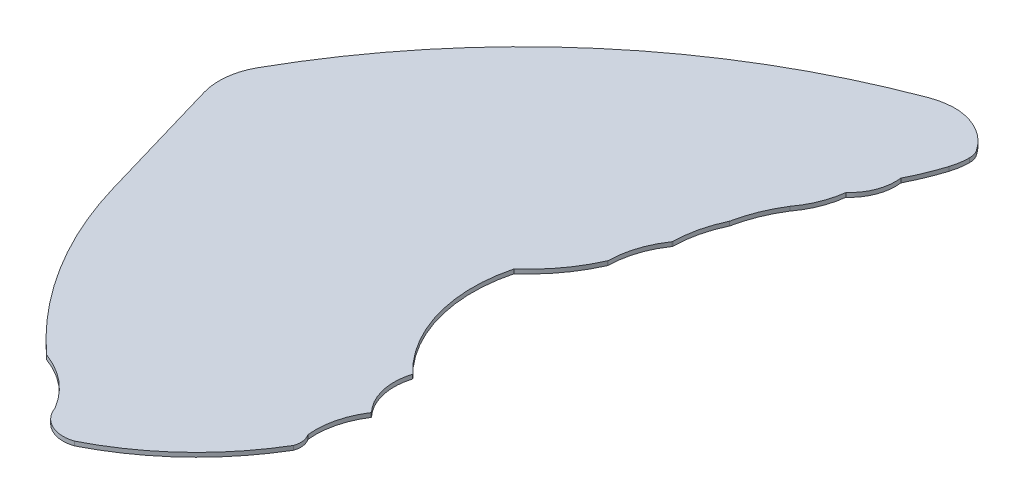
SolidWorks part; units mm, degrees
ref_plane "Plano frontal" through (0, 0, 0) normal (0, 0, 1) x (1, 0, 0)
ref_plane "Plano superior" through (0, 0, 0) normal (0, 1, 0) x (1, 0, 0)
ref_plane "Plano direito" through (0, 0, 0) normal (1, 0, 0) x (0, 0, -1)
sketch "Esboço1" plane through (0, 0, 0) normal (0, 1, 0) x (1, 0, 0)
  line L0 (245.8971, 320.852) -> (1229.6128, 320.852) construction
  line L1 (16.8906, -92.872) -> (-2.8919, -25.3314)
  line L3 (11.8593, -37.4647) -> (16.8906, -86.1328)
  arc A0 (-2.8919, -25.3314) -> (0, 0) centre (28.6286, -16.0991) cw
  arc A1 (0, 0) -> (189.3972, 162.1056) centre (316.3195, -177.8795) cw
  arc A3 (225.6385, 150.4697) -> (227.1081, 145.6019) centre (218.3116, 145.6019) cw construction
  arc A4 (227.1081, 145.6019) -> (225.6385, 136.1666) centre (196.0862, 145.6019) cw construction
  arc A5 (225.6385, 136.1666) -> (218.3116, 118.3563) centre (112.5985, 172.257) cw construction
  arc A7 (218.3116, 118.3563) -> (210.4763, 97.5461) centre (194.6459, 115.3865) cw construction
  arc A8 (210.4763, 97.5461) -> (202.0473, 76.5423) centre (166.9708, 102.8121) cw construction
  arc A9 (202.0473, 76.5423) -> (192.9964, 53.9892) centre (259.2241, 40.5039) ccw construction
  arc A10 (192.9964, 53.9892) -> (187.293, 29.7021) centre (245.6081, 28.8209) ccw construction
  arc A11 (187.293, 29.7021) -> (179.0373, 4.0907) centre (225.0788, 3.3859) ccw construction
  arc A12 (179.0373, 4.0907) -> (158.23, -24.0759) centre (104.6802, 37.2514) cw construction
  arc A15 (158.23, -24.0759) -> (13.4854, -32.4272) centre (93.7944, -165.8093) ccw construction
  arc A16 (158.23, -24.0759) -> (177.8517, -97.0522) centre (231.9136, -43.3901) ccw construction
  arc A17 (8.5132, -29.7405) -> (121.9031, 71.3535) centre (-285.6091, 414.2929) ccw construction
  arc A18 (11.0704, -33.894) -> (11.8796, -37.06) centre (11.8906, -35.3708) ccw
  arc A19 (69.7615, 17.5747) -> (179.0373, 4.0907) centre (83.0084, -324.6055) cw construction
  arc A20 (187.293, 29.7021) -> (90.5728, 37.2507) centre (111.635, -316.2908) ccw construction
  arc A21 (192.9964, 53.9892) -> (108.6142, 56.1566) centre (140.5341, -344.8129) ccw construction
  arc A22 (202.0473, 76.5423) -> (121.9031, 71.3535) centre (174.9731, -126.811) ccw construction
  arc A23 (121.9031, 71.3535) -> (117.6553, 87.2147) centre (137.0585, 83.9116) cw construction
  arc A24 (117.6553, 87.2147) -> (210.4763, 97.5461) centre (187.5432, -118.5488) cw construction
  arc A25 (202.7141, 163.713) -> (134.2312, 132.489) centre (289.7224, -117.8339) ccw
  arc A26 (65.7605, 73.6867) -> (134.9405, 112.1301) centre (303.5466, -272.7489) cw construction
  arc A27 (117.6553, 87.2147) -> (104.9295, 97.5363) centre (122.326, 105.9791) cw construction
  arc A28 (105.0708, 97.8389) -> (131.9285, 131.0439) centre (185.93, 59.9007) cw construction
  arc A29 (134.9405, 112.1301) -> (195.1764, 136.1273) centre (199.9365, 36.5807) cw construction
  arc A30 (134.9405, 112.1301) -> (218.3116, 118.3563) centre (194.9004, -129.4588) cw construction
  arc A31 (195.1764, 136.1273) -> (225.6385, 136.1666) centre (210.8302, -191.2388) cw construction
  arc A32 (164.2786, -78.4304) -> (163.8648, -78.0625) centre (76.6095, -176.6501) ccw construction
  arc A33 (40.2619, -50.4484) -> (16.8906, -86.1328) centre (54.6574, -85.3723) ccw
  arc A34 (11.8377, -37.2556) -> (39.3063, -38.1782) centre (28.1448, 38.8778) ccw construction
  arc A35 (39.3063, -38.1782) -> (77.0189, -29.7405) centre (80.4783, -133.7) cw construction
  arc A36 (77.0189, -29.7405) -> (145.0691, -29.7551) centre (110.9705, -372.2463) cw construction
  arc A37 (145.0691, -29.7551) -> (158.23, -24.0759) centre (145.2218, -12.02) ccw construction
  arc A38 (53.1607, -33.3342) -> (13.4854, -32.4272) centre (32.4211, -72.3358) ccw construction
  arc A39 (38.8997, -20.1148) -> (13.4854, -32.4272) centre (28.6163, -31.2738) cw construction
  arc A40 (16.8906, -92.872) -> (74.9246, -185.6146) centre (210.7556, -36.0892) ccw
  arc A41 (74.9929, -185.4267) -> (66.3816, -175.3804) centre (154.2645, -108.7641) cw construction
  arc A42 (39.4144, -134.6037) -> (75.0612, -185.2387) centre (266.3145, -12.7322) ccw
  arc A43 (74.9929, -185.4267) -> (101.4999, -207.5656) centre (57.6789, -233.0946) cw construction
  arc A44 (101.4999, -207.5656) -> (121.3412, -217.2503) centre (116.2629, -202.4873) ccw construction
  arc A45 (121.3412, -217.2503) -> (180.55, -161.9238) centre (55.9487, -87.924) ccw construction
  arc A46 (180.55, -161.9238) -> (179.3854, -153.5104) centre (171.7806, -158.8504) ccw construction
  arc A47 (179.3754, -98.5448) -> (185.959, -126.7273) centre (206.845, -106.9879) ccw construction
  arc A48 (185.959, -126.7273) -> (179.3854, -153.5104) centre (220.4313, -149.3865) ccw construction
  arc A49 (103.607, -114.0548) -> (179.3854, -153.5104) centre (-25.2756, -454.0845) cw construction
  arc A50 (55.95, -55.4784) -> (133.7088, -58.3585) centre (90.2455, -180.677) cw
  arc A51 (55.95, -55.4784) -> (31.1326, -75.9422) centre (66.32, -93.3351) ccw
  arc A52 (27.5649, -99.5565) -> (39.4144, -134.6037) centre (137.5319, -81.9033) ccw
  arc A53 (27.565, -87.1132) -> (73.2426, -117.5725) centre (461.4317, 514.0462) ccw construction
  arc A54 (73.2426, -117.5725) -> (92.998, -121.4212) centre (73.3114, -169.8452) cw construction
  arc A55 (92.998, -121.4212) -> (99.4217, -119.9985) centre (98.6915, -131.9152) cw construction
  arc A56 (99.4217, -119.9985) -> (103.607, -114.0548) centre (110.0937, -123.0679) cw construction
  arc A57 (103.607, -114.0548) -> (98.6915, -96.0121) centre (125.3192, -98.4486) cw construction
  arc A58 (98.6915, -96.0121) -> (77.4929, -81.9059) centre (103.8031, -65.3487) cw construction
  arc A59 (77.4929, -81.9059) -> (178.9645, -98.1504) centre (113.3271, -183.1111) cw construction
  arc A60 (77.4929, -81.9059) -> (31.0432, -76.1242) centre (71.4634, 59.1311) cw construction
  arc A61 (98.6915, -96.0121) -> (185.959, -126.7273) centre (76.8879, -297.2892) cw construction
  arc A62 (99.4217, -119.9985) -> (165.2455, -183.0853) centre (-749.6332, -1071.7733) cw construction
  arc A63 (92.998, -121.4212) -> (144.3602, -202.7494) centre (428.3218, 33.4673) ccw construction
  arc A64 (73.2426, -117.5725) -> (121.3412, -217.2503) centre (570.6991, 61.0271) ccw construction
  arc A65 (8.6464, -29.8922) -> (10.8842, -33.7922) centre (9.8905, -31.7703) ccw
  arc A66 (65.8737, 73.5218) -> (65.1633, 72.9862) centre (71.5226, 65.2919) ccw
  arc A67 (104.7763, 97.681) -> (130.1059, 129.8789) centre (185.93, 59.9007) cw
  arc A68 (104.7481, 97.6206) -> (150.4255, 142.0756) centre (185.93, 59.9007) cw construction
  arc A69 (104.9295, 97.5363) -> (150.5048, 141.892) centre (185.93, 59.9007) cw construction
  arc A70 (130.1059, 129.8789) -> (66.2643, 74.2743) centre (289.7224, -117.8339) ccw
  arc A71 (65.1633, 72.9862) -> (8.6083, -29.4376) centre (289.7224, -117.8339) ccw
  arc A72 (135.7135, 112.5265) -> (195.186, 135.9275) centre (199.9365, 36.5807) cw
  arc A73 (134.8328, 112.3013) -> (195.1668, 136.3271) centre (199.9365, 36.5807) cw
  arc A74 (65.8737, 73.5218) -> (104.8415, 97.2621) centre (303.5466, -272.7489) cw
  arc A75 (66.2643, 74.2743) -> (104.7763, 97.681) centre (303.5466, -272.7489) cw
  arc A76 (105.3664, 97.9971) -> (134.2312, 132.489) centre (185.93, 59.9007) cw
  arc A77 (105.3664, 97.9971) -> (134.8328, 112.3013) centre (303.5466, -272.7489) cw
  arc A78 (65.6474, 73.8516) -> (134.8603, 112.3133) centre (303.5466, -272.7489) cw construction
  arc A79 (203.4113, 163.9275) -> (225.6385, 150.4697) centre (200.23, 133.5888) cw construction
  arc A80 (203.3904, 163.7286) -> (225.4719, 150.359) centre (200.23, 133.5888) cw
  arc A81 (203.4321, 164.1264) -> (225.805, 150.5804) centre (200.23, 133.5888) cw
  arc A82 (189.3972, 162.1056) -> (203.4321, 164.1264) centre (201.0573, 130.8716) cw
  arc A83 (203.3904, 163.7286) -> (202.7141, 163.713) centre (203.1131, 161.0838) ccw
  arc A84 (225.4719, 150.359) -> (226.9081, 145.6019) centre (218.3116, 145.6019) cw
  arc A85 (226.9081, 145.6019) -> (225.4941, 136.3733) centre (196.0862, 145.6019) cw
  arc A86 (225.805, 150.5804) -> (227.3081, 145.6019) centre (218.3116, 145.6019) cw
  arc A87 (227.3081, 145.6019) -> (225.829, 136.1058) centre (196.0862, 145.6019) cw
  arc A88 (195.186, 135.9275) -> (225.3682, 135.9786) centre (210.8302, -191.2388) cw
  arc A89 (195.1668, 136.3271) -> (225.4941, 136.3733) centre (210.8302, -191.2388) cw
  arc A90 (195.1668, 136.3271) -> (225.6475, 136.3664) centre (210.8302, -191.2388) cw construction
  arc A91 (226.9081, 145.6019) -> (225.4479, 136.2275) centre (196.0862, 145.6019) cw construction
  arc A92 (225.3682, 135.9786) -> (218.195, 118.5681) centre (112.5985, 172.257) cw
  arc A93 (135.0052, 111.9401) -> (218.1326, 118.1722) centre (194.9004, -129.4588) cw
  arc A94 (218.1326, 118.1722) -> (210.4094, 97.7543) centre (194.6459, 115.3865) cw
  arc A95 (225.829, 136.1058) -> (218.5176, 118.3201) centre (112.5985, 172.257) cw
  arc A96 (135.7135, 112.5265) -> (218.195, 118.5681) centre (194.9004, -129.4588) cw
  arc A97 (218.5176, 118.3201) -> (210.6657, 97.4469) centre (194.6459, 115.3865) cw
  arc A98 (225.4479, 136.2275) -> (218.1334, 118.4471) centre (112.5985, 172.257) cw construction
  arc A99 (134.8923, 112.3242) -> (218.3304, 118.5554) centre (194.9004, -129.4588) cw construction
  arc A100 (195.186, 135.9275) -> (225.6294, 135.9669) centre (210.8302, -191.2388) cw construction
  arc A101 (134.8101, 112.2817) -> (195.1668, 136.3271) centre (199.9365, 36.5807) cw construction
  arc A102 (135.0709, 111.9785) -> (195.186, 135.9275) centre (199.9365, 36.5807) cw construction
  arc A103 (134.9887, 111.936) -> (218.2928, 118.1572) centre (194.9004, -129.4588) cw construction
  arc A104 (65.8737, 73.5218) -> (135.0208, 111.9469) centre (303.5466, -272.7489) cw construction
  arc A105 (218.51, 118.3812) -> (210.6091, 97.3965) centre (194.6459, 115.3865) cw construction
  arc A106 (225.829, 136.1058) -> (218.4898, 118.2654) centre (112.5985, 172.257) cw construction
  arc A107 (218.1131, 118.3314) -> (210.3436, 97.6957) centre (194.6459, 115.3865) cw construction
  arc A108 (117.6468, 87.423) -> (105.1942, 97.4512) centre (122.326, 105.9791) cw
  arc A109 (121.9757, 71.58) -> (117.8329, 87.0637) centre (137.0585, 83.9116) cw
  arc A110 (117.8329, 87.0637) -> (210.2529, 97.3685) centre (187.5432, -118.5488) cw
  arc A111 (210.2529, 97.3685) -> (201.9573, 76.7561) centre (166.9708, 102.8121) cw
  arc A112 (117.428, 87.066) -> (104.8415, 97.2621) centre (122.326, 105.9791) cw
  arc A113 (121.643, 71.3551) -> (117.428, 87.066) centre (137.0585, 83.9116) cw
  arc A114 (117.6468, 87.423) -> (210.4094, 97.7543) centre (187.5432, -118.5488) cw
  arc A115 (210.6657, 97.4469) -> (202.2122, 76.4289) centre (166.9708, 102.8121) cw
  arc A116 (105.1942, 97.4512) -> (135.0052, 111.9401) centre (303.5466, -272.7489) cw
  arc A117 (117.607, 87.0206) -> (104.7496, 97.449) centre (122.326, 105.9791) cw construction
  arc A118 (117.7036, 87.4087) -> (105.1094, 97.6236) centre (122.326, 105.9791) cw construction
  arc A119 (121.7491, 71.2259) -> (117.4582, 87.2482) centre (137.0585, 83.9116) cw construction
  arc A120 (117.7197, 87.0253) -> (210.2529, 97.3685) centre (187.5432, -118.5488) cw construction
  arc A121 (122.0571, 71.4811) -> (117.8525, 87.1811) centre (137.0585, 83.9116) cw construction
  arc A122 (117.591, 87.404) -> (210.6988, 97.7235) centre (187.5432, -118.5488) cw construction
  arc A123 (201.7125, 76.3849) -> (192.8379, 54.2118) centre (259.2241, 40.5039) ccw
  arc A124 (210.6988, 97.7235) -> (202.2073, 76.4225) centre (166.9708, 102.8121) cw construction
  arc A125 (202.2122, 76.4289) -> (193.1924, 53.9493) centre (259.2241, 40.5039) ccw
  arc A126 (201.9573, 76.7561) -> (121.9757, 71.58) centre (174.9731, -126.811) ccw
  arc A127 (193.1924, 53.9493) -> (193.1768, 53.9029) centre (192.9964, 53.9892) cw
  arc A128 (8.6464, -29.8922) -> (69.8412, 17.3776) centre (-285.6091, 414.2929) ccw
  arc A129 (8.6083, -29.4376) -> (121.643, 71.3551) centre (-285.6091, 414.2929) ccw
  arc A130 (192.8379, 54.2118) -> (109.1013, 56.3957) centre (140.5341, -344.8129) ccw
  arc A131 (202.2165, 76.4357) -> (193.1924, 53.9493) centre (259.2241, 40.5039) ccw construction
  arc A132 (8.4027, -29.5738) -> (121.7501, 71.4823) centre (-285.6091, 414.2929) ccw construction
  arc A133 (202.0737, 76.7406) -> (121.8513, 71.5467) centre (174.9731, -126.811) ccw construction
  arc A134 (187.0972, 29.9495) -> (91.0867, 37.4813) centre (111.635, -316.2908) ccw
  arc A135 (8.6236, -29.9073) -> (122.0561, 71.2247) centre (-285.6091, 414.2929) ccw construction
  arc A136 (193.0225, 54.1875) -> (108.5983, 56.356) centre (140.5341, -344.8129) ccw construction
  arc A137 (69.8412, 17.3776) -> (178.761, 3.963) centre (83.0084, -324.6055) cw
  arc A138 (109.1013, 56.3957) -> (122.0156, 71.1766) centre (-285.6091, 414.2929) ccw
  arc A139 (201.8781, 76.649) -> (192.8004, 54.0291) centre (259.2241, 40.5039) ccw construction
  arc A140 (210.2529, 97.3685) -> (201.8872, 76.6622) centre (166.9708, 102.8121) cw construction
  arc A141 (201.7125, 76.3849) -> (122.0156, 71.1766) centre (174.9731, -126.811) ccw
  arc A142 (193.1768, 53.9029) -> (187.4952, 29.8402) centre (245.6081, 28.8209) ccw
  arc A143 (187.3768, 29.4721) -> (187.4952, 29.8402) centre (186.8279, 29.8519) ccw
  arc A144 (187.0972, 29.9495) -> (90.5609, 37.4504) centre (111.635, -316.2908) ccw construction
  arc A145 (91.0867, 37.4813) -> (108.709, 55.9635) centre (-285.6091, 414.2929) ccw
  arc A146 (187.4898, 29.4542) -> (90.5847, 37.0511) centre (111.635, -316.2908) ccw construction
  arc A147 (192.6977, 53.8267) -> (187.0972, 29.9495) centre (245.6081, 28.8209) ccw
  arc A148 (192.816, 54.0755) -> (187.0972, 29.9495) centre (245.6081, 28.8209) ccw construction
  arc A149 (192.6977, 53.8267) -> (108.709, 55.9635) centre (140.5341, -344.8129) ccw
  arc A150 (187.3768, 29.4721) -> (179.2373, 4.0876) centre (225.0788, 3.3859) ccw
  arc A151 (70.3073, 17.7955) -> (178.8421, 4.356) centre (83.0084, -324.6055) cw
  arc A152 (186.9587, 29.5703) -> (178.8421, 4.356) centre (225.0788, 3.3859) ccw
  arc A153 (69.7538, 17.7745) -> (178.8421, 4.356) centre (83.0084, -324.6055) cw construction
  arc A154 (70.3073, 17.7955) -> (90.6603, 37.0556) centre (-285.6091, 414.2929) ccw
  arc A155 (69.7692, 17.3748) -> (179.2341, 3.8248) centre (83.0084, -324.6055) cw construction
  arc A156 (187.1288, 29.8164) -> (178.8421, 4.356) centre (225.0788, 3.3859) ccw construction
  arc A157 (186.9587, 29.5703) -> (90.6603, 37.0556) centre (111.635, -316.2908) ccw
  arc A158 (187.4571, 29.5878) -> (179.2341, 3.8248) centre (225.0788, 3.3859) ccw construction
  arc A159 (193.1768, 53.9029) -> (187.4898, 29.4542) centre (245.6081, 28.8209) ccw construction
  arc A160 (178.8547, 4.1721) -> (178.8436, 4.1472) centre (104.6802, 37.2514) cw
  arc A161 (158.1953, -23.8405) -> (10.8842, -33.7922) centre (93.7944, -165.8093) ccw
  arc A162 (179.22, 4.0092) -> (158.4079, -24.186) centre (104.6802, 37.2514) cw
  arc A163 (179.22, 4.0092) -> (158.2644, -24.3113) centre (104.6802, 37.2514) cw construction
  arc A165 (158.1953, -23.8405) -> (13.3822, -32.2559) centre (93.7944, -165.8093) ccw construction
  arc A167 (53.1846, -33.1205) -> (16.3441, -30.9777) centre (32.4211, -72.3358) ccw
  arc A168 (11.8593, -37.4647) -> (39.3612, -38.3724) centre (28.1448, 38.8778) ccw
  arc A169 (39.3612, -38.3724) -> (77.0321, -29.9402) centre (80.4783, -133.7) cw
  arc A170 (77.0321, -29.9402) -> (145.0582, -29.9551) centre (110.9705, -372.2463) cw
  arc A171 (145.0582, -29.9551) -> (157.8482, -24.7583) centre (145.2218, -12.02) ccw
  arc A172 (145.0582, -29.9551) -> (158.3767, -24.2119) centre (145.2218, -12.02) ccw construction
  arc A173 (11.8796, -37.06) -> (39.2515, -37.9841) centre (28.1448, 38.8778) ccw
  arc A174 (39.2515, -37.9841) -> (52.6186, -33.2758) centre (80.4783, -133.7) cw
  arc A175 (77.0057, -29.5409) -> (145.0798, -29.5552) centre (110.9705, -372.2463) cw
  arc A176 (145.0798, -29.5552) -> (157.8927, -24.1424) centre (145.2218, -12.02) ccw
  arc A177 (53.2546, -33.1576) -> (13.3997, -32.2465) centre (32.4211, -72.3358) ccw construction
  arc A178 (11.7958, -37.4511) -> (39.3612, -38.3724) centre (28.1448, 38.8778) ccw construction
  arc A179 (158.2644, -24.3113) -> (13.5886, -32.5986) centre (93.7944, -165.8093) ccw construction
  arc A180 (145.0798, -29.5552) -> (158.0833, -23.94) centre (145.2218, -12.02) ccw construction
  arc A182 (52.6186, -33.2758) -> (11.0704, -33.894) centre (32.4211, -72.3358) ccw
  arc A183 (53.1846, -33.1205) -> (77.0057, -29.5409) centre (80.4783, -133.7) cw
  arc A184 (39.2515, -37.9841) -> (77.0057, -29.5409) centre (80.4783, -133.7) cw construction
  arc A185 (157.8927, -24.1424) -> (16.3441, -30.9777) centre (93.7944, -165.8093) ccw
  arc A186 (178.761, 3.963) -> (158.1953, -23.8405) centre (104.6802, 37.2514) cw
  arc A187 (178.8547, 4.1721) -> (158.1953, -23.8405) centre (104.6802, 37.2514) cw construction
  arc A188 (179.22, 4.0092) -> (179.2373, 4.0876) centre (179.0373, 4.0907) ccw
  arc A189 (157.8482, -24.7583) -> (163.5415, -77.4206) centre (231.9136, -43.3901) ccw
  arc A190 (158.4079, -24.186) -> (179.5133, -98.4) centre (231.9136, -43.3901) ccw
  arc A191 (158.0365, -24.0252) -> (179.2374, -98.6896) centre (231.9136, -43.3901) ccw construction
  arc A192 (133.8427, -57.9816) -> (40.2619, -50.4484) centre (75.882, -192.9794) ccw
  arc A193 (158.4235, -24.1266) -> (179.5133, -98.4) centre (231.9136, -43.3901) ccw construction
  arc A194 (133.7758, -58.17) -> (163.8648, -78.0625) centre (108.6533, -128.872) cw construction
  arc A195 (133.7088, -58.3585) -> (163.7246, -78.2055) centre (108.6533, -128.872) cw
  arc A196 (163.7246, -78.2055) -> (164.2392, -78.7877) centre (149.3526, -91.428) cw
  arc A197 (133.8427, -57.9816) -> (163.5415, -77.4206) centre (108.6533, -128.872) cw
  arc A198 (77.3856, -82.1106) -> (30.9549, -76.3065) centre (71.4634, 59.1311) cw
  arc A199 (133.8427, -57.9816) -> (164.005, -77.9196) centre (108.6533, -128.872) cw construction
  arc A200 (164.1455, -78.5796) -> (163.7246, -78.2055) centre (76.6095, -176.6501) ccw construction
  arc A201 (164.2392, -78.7877) -> (176.8413, -96.3038) centre (231.9136, -43.3901) ccw
  arc A202 (164.4118, -78.2811) -> (164.005, -77.9196) centre (76.6095, -176.6501) ccw construction
  arc A203 (77.7964, -82.0109) -> (178.8422, -98.3087) centre (113.3271, -183.1111) cw
  arc A204 (77.4544, -81.7073) -> (31.1326, -75.9422) centre (71.4634, 59.1311) cw
  arc A205 (77.4544, -81.7073) -> (176.8413, -96.3038) centre (113.3271, -183.1111) cw
  arc A206 (77.5314, -82.1044) -> (30.986, -76.3158) centre (71.4634, 59.1311) cw construction
  arc A207 (30.9549, -76.3065) -> (27.6041, -86.8743) centre (66.32, -93.3351) ccw
  arc A208 (77.4544, -81.7073) -> (31.1005, -75.9326) centre (71.4634, 59.1311) cw construction
  arc A209 (158.23, -24.0759) -> (179.3754, -98.5448) centre (231.9136, -43.3901) ccw construction
  arc A210 (98.7187, -95.8139) -> (77.7964, -82.0109) centre (103.8031, -65.3487) cw
  arc A211 (103.7344, -113.8892) -> (98.8729, -96.233) centre (125.3192, -98.4486) cw
  arc A212 (98.713, -95.8133) -> (184.8389, -125.7798) centre (76.8879, -297.2892) cw construction
  arc A213 (179.5665, -98.6035) -> (185.9696, -126.4464) centre (206.845, -106.9879) ccw
  arc A214 (98.4761, -96.1784) -> (77.3856, -82.1106) centre (103.8031, -65.3487) cw
  arc A215 (103.3296, -114.0103) -> (98.4761, -96.1784) centre (125.3192, -98.4486) cw
  arc A216 (98.7187, -95.8139) -> (184.8389, -125.7798) centre (76.8879, -297.2892) cw
  arc A217 (179.5133, -98.4) -> (179.5665, -98.6035) centre (179.3754, -98.5448) cw
  arc A218 (98.6586, -96.2094) -> (77.3236, -82.0124) centre (103.8031, -65.3487) cw construction
  arc A219 (77.5314, -82.1044) -> (178.8422, -98.3087) centre (113.3271, -183.1111) cw construction
  arc A220 (178.8422, -98.3087) -> (179.0485, -98.9406) centre (178.4809, -98.7763) cw
  arc A221 (98.7244, -95.8148) -> (77.6621, -81.7994) centre (103.8031, -65.3487) cw construction
  arc A222 (77.4544, -81.7073) -> (179.0867, -97.9922) centre (113.3271, -183.1111) cw construction
  arc A223 (99.6493, -119.9335) -> (103.6372, -114.2802) centre (110.0937, -123.0679) cw
  arc A224 (179.0485, -98.9406) -> (184.8389, -125.7798) centre (206.845, -106.9879) ccw
  arc A225 (179.1842, -98.486) -> (184.8389, -125.7798) centre (206.845, -106.9879) ccw construction
  arc A226 (103.6372, -114.2802) -> (179.2425, -153.6551) centre (-25.2756, -454.0845) cw
  arc A227 (186.018, -127.0026) -> (179.5792, -153.4387) centre (220.4313, -149.3865) ccw
  arc A228 (99.2747, -119.7902) -> (103.3296, -114.0103) centre (110.0937, -123.0679) cw
  arc A229 (103.7344, -113.8892) -> (179.1459, -153.1057) centre (-25.2756, -454.0845) cw
  arc A230 (185.7919, -126.6175) -> (185.7905, -126.6196) centre (220.4313, -149.3865) ccw
  arc A231 (184.6648, -128.4325) -> (179.1459, -153.1057) centre (220.4313, -149.3865) ccw
  arc A232 (185.7919, -126.6175) -> (179.1459, -153.1057) centre (220.4313, -149.3865) ccw construction
  arc A233 (186.1262, -126.8372) -> (179.6297, -153.919) centre (220.4313, -149.3865) ccw construction
  arc A234 (98.6699, -96.2109) -> (187.474, -127.9445) centre (76.8879, -297.2892) cw construction
  arc A235 (186.018, -127.0026) -> (185.9696, -126.4464) centre (185.6381, -126.7554) ccw
  arc A236 (179.5665, -98.6035) -> (187.474, -127.9445) centre (206.845, -106.9879) ccw construction
  arc A237 (184.6648, -128.4325) -> (183.9983, -125.7249) centre (182.9391, -127.4215) ccw
  arc A238 (93.2588, -121.5089) -> (99.3405, -120.1941) centre (98.6915, -131.9152) cw
  arc A239 (99.3405, -120.1941) -> (164.9738, -183.0926) centre (-749.6332, -1071.7733) cw
  arc A240 (121.4315, -217.4287) -> (180.7321, -162.0089) centre (55.9487, -87.924) ccw
  arc A241 (180.7321, -162.0089) -> (179.5792, -153.4387) centre (171.7806, -158.8504) ccw
  arc A242 (92.986, -121.2005) -> (99.2747, -119.7902) centre (98.6915, -131.9152) cw
  arc A243 (99.6493, -119.9335) -> (165.2373, -182.7899) centre (-749.6332, -1071.7733) cw
  arc A244 (121.4146, -216.9889) -> (144.0736, -202.7175) centre (55.9487, -87.924) ccw
  arc A245 (180.3678, -161.8389) -> (179.2425, -153.6551) centre (171.7806, -158.8504) ccw
  arc A246 (99.2295, -119.9432) -> (103.578, -113.83) centre (110.0937, -123.0679) cw construction
  arc A247 (103.578, -113.83) -> (179.1459, -153.1057) centre (-25.2756, -454.0845) cw construction
  arc A248 (92.9026, -121.2454) -> (99.5034, -119.8034) centre (98.6915, -131.9152) cw construction
  arc A249 (99.6139, -120.0538) -> (103.6372, -114.2802) centre (110.0937, -123.0679) cw construction
  arc A250 (99.5034, -119.8034) -> (165.389, -182.9459) centre (-749.6332, -1071.7733) cw construction
  arc A251 (103.7694, -113.9381) -> (98.8906, -96.0303) centre (125.3192, -98.4486) cw construction
  arc A252 (103.4446, -114.1716) -> (98.4923, -95.9939) centre (125.3192, -98.4486) cw construction
  arc A253 (180.3678, -161.8389) -> (179.2217, -153.6253) centre (171.7806, -158.8504) ccw construction
  arc A254 (98.8729, -96.233) -> (183.9983, -125.7249) centre (76.8879, -297.2892) cw
  arc A255 (103.6372, -114.2802) -> (179.6297, -153.919) centre (-25.2756, -454.0845) cw construction
  arc A256 (180.7321, -162.0089) -> (179.549, -153.3955) centre (171.7806, -158.8504) ccw construction
  arc A257 (165.3772, -182.9338) -> (165.389, -182.9459) centre (-749.6332, -1071.7733) cw
  arc A258 (165.2373, -182.7899) -> (180.3678, -161.8389) centre (55.9487, -87.924) ccw
  arc A259 (121.251, -217.0718) -> (180.3678, -161.8389) centre (55.9487, -87.924) ccw construction
  arc A260 (99.3405, -120.1941) -> (165.102, -183.2246) centre (-749.6332, -1071.7733) cw construction
  arc A261 (121.4315, -217.4287) -> (121.4146, -217.4365) centre (121.315, -217.1984) cw
  arc A262 (92.8496, -121.5768) -> (144.0736, -202.7175) centre (428.3218, 33.4673) ccw
  arc A263 (73.2991, -117.3724) -> (92.986, -121.2005) centre (73.3114, -169.8452) cw
  arc A264 (93.2588, -121.5089) -> (144.3907, -202.4733) centre (428.3218, 33.4673) ccw
  arc A265 (73.2423, -117.3725) -> (93.1465, -121.2657) centre (73.3114, -169.8452) cw construction
  arc A266 (93.1465, -121.2657) -> (144.5139, -202.6215) centre (428.3218, 33.4673) ccw construction
  arc A267 (93.0933, -121.597) -> (99.3405, -120.1941) centre (98.6915, -131.9152) cw construction
  arc A268 (144.3907, -202.4733) -> (164.9738, -183.0926) centre (55.9487, -87.924) ccw
  arc A269 (74.9246, -185.6146) -> (101.3172, -207.6494) centre (57.6789, -233.0946) cw
  arc A270 (92.8496, -121.5768) -> (144.2064, -202.8773) centre (428.3218, 33.4673) ccw construction
  arc A271 (101.3172, -207.6494) -> (121.4146, -217.4365) centre (116.2629, -202.4873) ccw
  arc A272 (73.5271, -117.7729) -> (121.4146, -216.9889) centre (570.6991, 61.0271) ccw
  arc A273 (27.682, -86.951) -> (73.2991, -117.3724) centre (461.4317, 514.0462) ccw
  arc A274 (75.0612, -185.2387) -> (101.6826, -207.482) centre (57.6789, -233.0946) cw
  arc A275 (101.6826, -207.482) -> (121.0383, -217.1408) centre (116.2629, -202.4873) ccw
  arc A276 (73.0781, -117.7061) -> (121.0383, -217.1408) centre (570.6991, 61.0271) ccw
  arc A277 (27.5301, -87.3346) -> (73.0781, -117.7061) centre (461.4317, 514.0462) ccw
  arc A278 (27.682, -86.951) -> (27.6041, -86.8743) centre (27.8932, -86.6584) cw
  arc A279 (27.5301, -87.3346) -> (27.5649, -99.5565) centre (66.32, -93.3351) ccw
  arc A280 (27.4479, -87.2753) -> (73.0781, -117.7061) centre (461.4317, 514.0462) ccw construction
  arc A281 (27.682, -86.951) -> (73.4071, -117.4388) centre (461.4317, 514.0462) ccw construction
  arc A282 (73.4071, -117.4388) -> (121.6421, -217.3562) centre (570.6991, 61.0271) ccw construction
  arc A283 (73.5271, -117.7729) -> (92.8496, -121.5768) centre (73.3114, -169.8452) cw
  arc A284 (73.2428, -117.7725) -> (92.8496, -121.5768) centre (73.3114, -169.8452) cw construction
  arc A285 (101.3172, -207.6494) -> (121.6421, -217.3562) centre (116.2629, -202.4873) ccw construction
  dimension "D2" = 0.2
  dimension "D3" = 0.2
  dimension "D4" = 0.2
  dimension "D5" = 0.2
  dimension "D41" = 2
  dimension "D1" = 230
  dimension "D6" = 0.2
  dimension "D7" = 0.2
  dimension "D8" = 0.2
  dimension "D9" = 0.2
  dimension "D10" = 0.2
  dimension "D11" = 0.2
  dimension "D12" = 0.2
  dimension "D13" = 0.2
  dimension "D14" = 0.2
  dimension "D15" = 0.2
  dimension "D16" = 0.2
  dimension "D17" = 0.2
  dimension "D18" = 0.2
  dimension "D19" = 0.2
  dimension "D20" = 0.2
  dimension "D21" = 0.2
  dimension "D22" = 0.2
  dimension "D23" = 0.2
  dimension "D24" = 0.2
  dimension "D25" = 0.2
  dimension "D26" = 0.2
  dimension "D27" = 0.2
  dimension "D28" = 0.2
  dimension "D29" = 0.2
  dimension "D30" = 0.2
  dimension "D31" = 0.2
  dimension "D32" = 0.2
  dimension "D33" = 0.2
  dimension "D34" = 0.2
  dimension "D35" = 0.2
  dimension "D36" = 0.2
  dimension "D37" = 0.2
  dimension "D38" = 0.2
  dimension "D39" = 0.2
  dimension "D40" = 0.2
  dimension "D42" = 0.2
  dimension "D43" = 0.2
  dimension "D44" = 0.2
  dimension "D45" = 0.2
  dimension "D46" = 0.2
  dimension "D47" = 0.2
extrude "Ressalto-extrusão1" add sketch "Esboço1" along normal blind 2 contours A269 A271 A261 A240 A241 A227 A235 A213 A217 A190 A162 A188 A150 A143 A142 A127 A125 A115 A97 A95 A87 A86 A81 A82 A1 A0 L1 A40 A279 A277 A276 A275 A274 A42 A52 A211 A254 A237 A231 A229 region at (11.2903, 0, 57.8449)
extrude "Ressalto-extrusão2" add sketch "Esboço1<3>" along normal blind 0.2 from surface contours A186 A137 A128 A65 A161 | A152 A157 A154 A151 | A176 A185 A167 A183 A175 | A192 A197 A189 A171 A170 A169 A168 L3 A33 | A71 A129 A113 A112 A74 A66 | A269 A271 A261 A240 A241 A227 A235 A213 A217 A190 A162 A188 A150 A143 A142 A127 A125 A115 A97 A95 A87 A86 A81 A82 A1 A0 L1 A40 A279 A277 A276 A275 A274 A42 A52 A211 A254 A237 A231 A229 | A174 A182 A18 A173 | A204 A205 A201 A196 A195 A50 A51 | A278 A273 A263 A242 A228 A215 A214 A198 A207 | A224 A220 A203 A210 A216 | A254 A211 A229 A231 A237 | A243 A258 A245 A226 A223 | A264 A268 A239 A238 | A283 A272 A244 A262 | A277 A279 A52 A42 A274 A275 A276 | A147 A149 A145 A134 | A123 A141 A138 A130 | A126 A111 A110 A109 | A116 A108 A114 A94 A93 | A70 A75 A67 | A73 A89 A85 A84 A80 A83 A25 A76 A77 | A72 A96 A92 A88 region at (11.2903, 0, 57.8449) region at (93.3314, 0, 44.0299) region at (30.2552, 0, 33.7407) region at (172.6853, 0, -137.9057) region at (68.277, 0, 149.0902) region at (96.0423, 0, 67.887) region at (105.3792, 0, 1.9385) region at (67.7343, 0, -41.6275) region at (97.2183, 0, -100.0776) region at (187.8294, 0, -126.0632) region at (164.9938, 0, -105.5934) region at (164.8699, 0, -86.5072) region at (159.7192, 0, -66.532) region at (147.0548, 0, -45.7562) region at (134.2713, 0, -24.2683) region at (91.1356, 0, 21.4792) region at (68.1743, 0, 98.0108) region at (134.8048, 0, 93.3656) region at (144.5463, 0, 120.4893) region at (145.9958, 0, 147.7646) region at (130.5494, 0, 164.4613) region at (107.9431, 0, 169.4007) starting at face at (65.5699, 2, 150.5627)
sketch "Esboço1<3>" plane through (0, 0, 0) normal (0, 1, 0) x (1, 0, 0) same geometry as "Esboço1"
sketch "Esboço3" plane through (0, 0, 0) normal (0, 1, 0) x (1, 0, 0)
  line L1 (-5.5, 11.12) -> (8, 11.12)
  line L2 (-5.5, 11.12) -> (-5.5, -30.63)
  line L3 (-5.5, -30.63) -> (8, -30.63)
  line L4 (8, 11.12) -> (8, -30.63)
  point P4 (0, 0)
  point P5 (0, 0)
  point P6 (0, 0)
  point P9 (0, 0)
  point P10 (0, 0)
  point P14 (0, 0)
  point P17 (0, 0)
  dimension "D1" = 11.12
  dimension "D2" = 30.63
  dimension "D3" = 5.5
  dimension "D4" = 8
extrude "Corte-extrusão2" cut sketch "Esboço3" along normal blind 0.2
